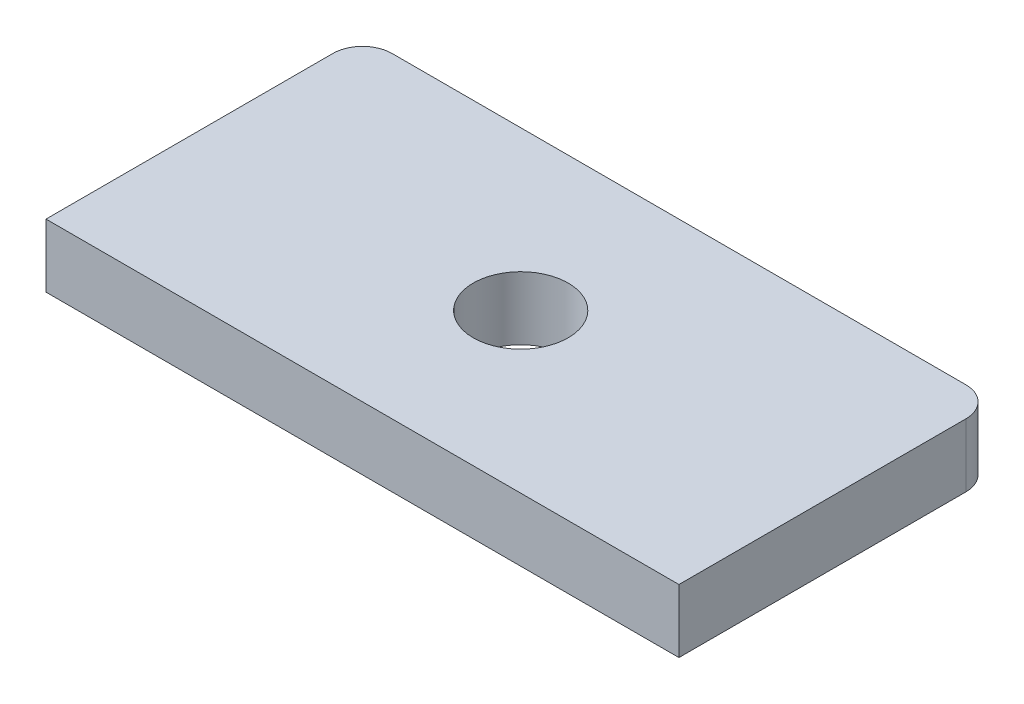
SolidWorks part; units mm, degrees
material "AISI 304"
ref_plane "Front Plane" through (0, 0, 0) normal (0, 0, 1) x (1, 0, 0)
ref_plane "Top Plane" through (0, 0, 0) normal (0, 1, 0) x (1, 0, 0)
ref_plane "Right Plane" through (0, 0, 0) normal (1, 0, 0) x (0, 0, -1)
sketch "Sketch1" plane through (0, 0, 0) normal (0, 1, 0) x (1, 0, 0)
  line L1 (40, -20) -> (-40, -20)
  line L2 (40, -20) -> (40, 20)
  line L3 (40, 20) -> (-40, 20)
  line L4 (-40, -20) -> (-40, 20)
  line L5 (40, -20) -> (-40, 20) construction
  line L6 (40, 20) -> (-40, -20) construction
  point P0 (0, 0)
  dimension "D1" = 40
  dimension "D2" = 80
base flange "Base-Flange1" sketch "Sketch1" thickness 8 reverse thickness direction no parameters "D1"=0.7366
sketch "Sketch6" plane through (0, 0, 0) normal (0, 1, 0) x (1, 0, 0)
  line L0 (-40, 20) -> (40, -20) construction
  line L1 (-40, -20) -> (40, -20) construction
  line L2 (40, -20) -> (-40, 20) construction
  line L3 (40, 20) -> (-40, -20) construction
  circle A0 centre (0, 0) radius 6
  dimension "D1" = 12
extrude "Cut-Extrude1" cut sketch "Sketch6" against normal blind 10
fillet "Fillet1" radius 3.74 2 edges at (40, -4, -20) (-40, -4, -20)
sketch "Bend-Lines1" [suppressed] plane through (0, 0, 0) normal (0, 1, 0) x (1, 0, 0)
sketch "Bounding-Box1" [suppressed] plane through (0, 0, 0) normal (0, 1, 0) x (1, 0, 0)
sheet metal parameters "Sheet-Metal1" thickness 8 parameters "D1"=0.7366
flat pattern "Flat-Pattern1" [suppressed]
sketch "Bend-Lines2" plane through (0, 0, 0) normal (0, 1, 0) x (1, 0, 0)
sketch3d "Bounding-Box2" [suppressed]
  line L0 (-40, -20, 0) -> (40, -20, 0) construction
  line L1 (-40, 20, 0) -> (40, 20, 0) construction
  line L2 (-40, -20, 0) -> (-40, 20, 0) construction
  line L3 (40, -20, 0) -> (40, 20, 0) construction
sheet metal parameters "Sheet-Metal2" thickness 8 parameters "D1"=0.7366
flat pattern "Flat-Pattern1"
sketch "Bend-Lines2" plane through (0, 0, 0) normal (0, 1, 0) x (1, 0, 0)
sketch3d "Bounding-Box2" [suppressed]
  line L0 (-40, -20, 0) -> (40, -20, 0) construction
  line L1 (-40, 20, 0) -> (40, 20, 0) construction
  line L2 (-40, -20, 0) -> (-40, 20, 0) construction
  line L3 (40, -20, 0) -> (40, 20, 0) construction
equation "\"thickness 1\" = 2"
equation "\"thickness radius 1\"= 3.7366"
equation "\"thickness 2\"= 3"
equation "\"connecting flange\"= 35"
equation "\"main length\"= 1200"
equation "\"main width\"= 1200"
equation "\"divider panel distance offset\"= 296"
equation "\"top panel slot length\"= 250"
equation "\"top panel slot width\"= 700"
equation "\"side panel length\"= 1200"
equation "\"side panel width\"= 950"
equation "\"access hatch length\" = \"access hatch cutout length\" + \"access hatch offset\" * 2"
equation "\"access hatch width\" = \"access hatch cutout width\" + \"access hatch offset\" * 2"
equation "\"access hatch offset X\"= 100"
equation "\"access hatch offset Y\"= 100"
equation "\"back panel access hatch length\"= 1150"
equation "\"back panel access hatch width\"= 206"
equation "\"back panel access hatch flange\"= 40"
equation "\"slotted panel length\" = \"main length\" + 100"
equation "\"slotted panel width\" = \"main width\""
equation "\"slot count x\"= 4"
equation "\"slot count y\"= 9"
equation "\"slot offset\" = \"water tray depth\""
equation "\"slot length\"= 30"
equation "\"slot width\"= 200"
equation "\"drift eliminator size offset\"= 5"
equation "\"drift eliminator length\"= \"back panel access hatch length\" - \"drift eliminator size offset\""
equation "\"drift eliminator width\"= \"back panel access hatch width\" - \"drift eliminator size offset\""
equation "\"drift eliminator depth\" = \"divider panel distance offset\""
equation "\"guide rail flange\"= 40"
equation "\"guid rail flange mount side\"= 20"
equation "\"guid rail back length\" = \"main width\" - \"guide rail flange\" * 2"
equation "\"splash plate length\"= 400"
equation "\"splash plate width\" = \"main width\""
equation "\"splash plate air gap\"= 200"
equation "\"splash plate slot count\"= 11"
equation "\"splash plate slot length\"= 50"
equation "\"splash plate slot height\"= 50"
equation "\"splash plate slot offset\"= 65"
equation "\"water tray depth\"= 150"
equation "\"water tray width\"= 200"
equation "\"dimpled panel length\" = \"main length\" - 200 - \"water tray depth\"/2"
equation "\"dimpled panel top offset\" = \"water tray depth\"/2"
equation "\"dimpled panel width\" = \"main width\""
equation "\"dimple panel slot count\"= 36"
equation "\"dimple panel slot length\"= 8"
equation "\"dimple panel slot width\"= 8"
equation "\"dimple panel slot offset\"= 25"
equation "\"sump base flat section width\"= 300"
equation "\"sump upper depth\"= 300"
equation "\"sump depth\"= 550"
equation "\"leg length\" = \"sump depth\" + 150"
equation "\"leg width\"= 80"
equation "\"leg depth\"= 40"
equation "\"leg base plate thickness\"= 8"
equation "\"slot offset x\" = \"slot length\" + \"slot offset\""
equation "\"slot offset y\" = \"slot width\" + \"slot offset\""
equation "\"leg support plate size\" = \"leg width\" - \"thickness 2\" * 2"
equation "\"D1@Sketch1\"=\"leg depth\""
equation "\"D2@Sketch1\"=\"leg width\""
